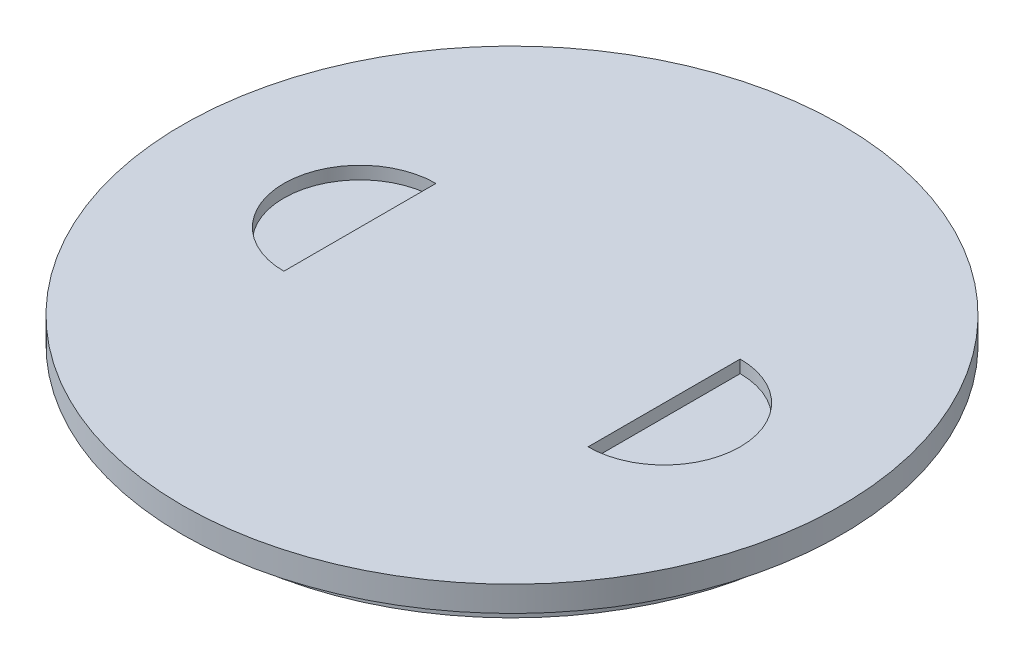
SolidWorks part; units mm, degrees
ref_plane "Front Plane" through (0, 0, 0) normal (0, 0, 1) x (1, 0, 0)
ref_plane "Top Plane" through (0, 0, 0) normal (0, 1, 0) x (1, 0, 0)
ref_plane "Right Plane" through (0, 0, 0) normal (1, 0, 0) x (0, 0, -1)
sketch "Sketch1" plane through (0, 0, 0) normal (0, 1, 0) x (1, 0, 0)
  circle A0 centre (0, 0) radius 82.55
  circle A1 centre (0, 0) radius 74.93
  circle A2 centre (0, 0) radius 69.85
  dimension "D1" = 165.1
  dimension "D2" = 149.86
  dimension "D3" = 139.7
extrude "Boss-Extrude2" add sketch "Sketch1" along normal blind 6.35 contours A2 | A1 A2 | A0 A1 region at (-80.2151, 0, 0) region at (-72.8107, 0, 0) region at (0, 0, 0)
extrude "Boss-Extrude3" add sketch "Sketch1<4>" against normal blind 6.35 contours A1 A2 region at (-72.8107, 0, 0)
sketch "Sketch1<4>" plane through (0, 0, 0) normal (0, 1, 0) x (1, 0, 0) same geometry as "Sketch1"
sketch "Sketch2" plane through (0, 6.35, 0) normal (0, 1, 0) x (1, 0, 0)
  line L0 (-38.1, 19.05) -> (-38.1, -19.05)
  line L1 (0, 0) -> (0, 16.4058) construction
  line L2 (38.1, 19.05) -> (38.1, -19.05)
  arc A0 (-38.1, 19.05) -> (-38.1, -19.05) centre (-38.1, 0) ccw
  arc A1 (38.1, 19.05) -> (38.1, -19.05) centre (38.1, 0) cw
  dimension "D1" = 38.1
  dimension "D2" = 38.1
extrude "Cut-Extrude1" cut sketch "Sketch2" against normal blind 3.175
